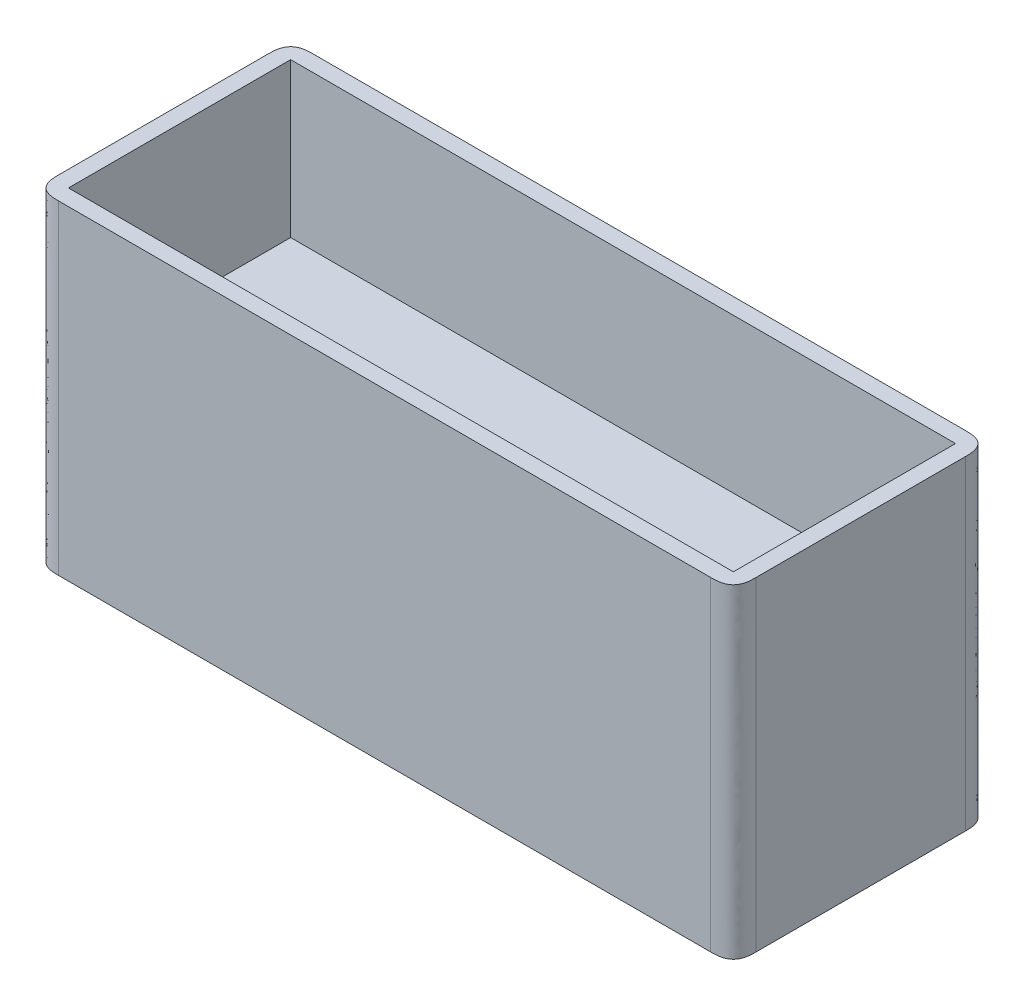
SolidWorks part; units mm, degrees
ref_plane "Front Plane" through (0, 0, 0) normal (0, 0, 1) x (1, 0, 0)
ref_plane "Top Plane" through (0, 0, 0) normal (0, 1, 0) x (1, 0, 0)
ref_plane "Right Plane" through (0, 0, 0) normal (1, 0, 0) x (0, 0, -1)
sketch "Sketch2" plane through (0, 0, 0) normal (0, 1, 0) x (1, 0, 0)
  line L0 (-107.5, 39.25) -> (107.5, 39.25)
  line L1 (-102.5, 34.25) -> (102.5, 34.25)
  line L2 (-102.5, 34.25) -> (-102.5, -34.25)
  line L3 (-102.5, -34.25) -> (102.5, -34.25)
  line L4 (102.5, 34.25) -> (102.5, -34.25)
  line L5 (-102.5, 34.25) -> (102.5, -34.25) construction
  line L6 (-102.5, -34.25) -> (102.5, 34.25) construction
  line L7 (107.5, 39.25) -> (107.5, -39.25)
  line L8 (-107.5, -39.25) -> (107.5, -39.25)
  line L9 (-107.5, 39.25) -> (-107.5, -39.25)
  point P0 (0, 0)
  dimension "D1" = 68.5
  dimension "D2" = 205
  dimension "D3" = 5
extrude "Boss-Extrude1" add sketch "Sketch2" along normal mid plane 100
extrude "Boss-Extrude2" add sketch "Sketch2<2>" along normal mid plane 5 contours L4 L1 L2 L3 region at (0, 0, 0)
sketch "Sketch2<2>" plane through (0, 0, 0) normal (0, 1, 0) x (1, 0, 0) same geometry as "Sketch2"
fillet "Fillet1" radius 7 4 edges at (-107.5, 0, -39.25) (-107.5, 0, 39.25) (107.5, 0, 39.25) (107.5, 0, -39.25) curvature continuous yes
